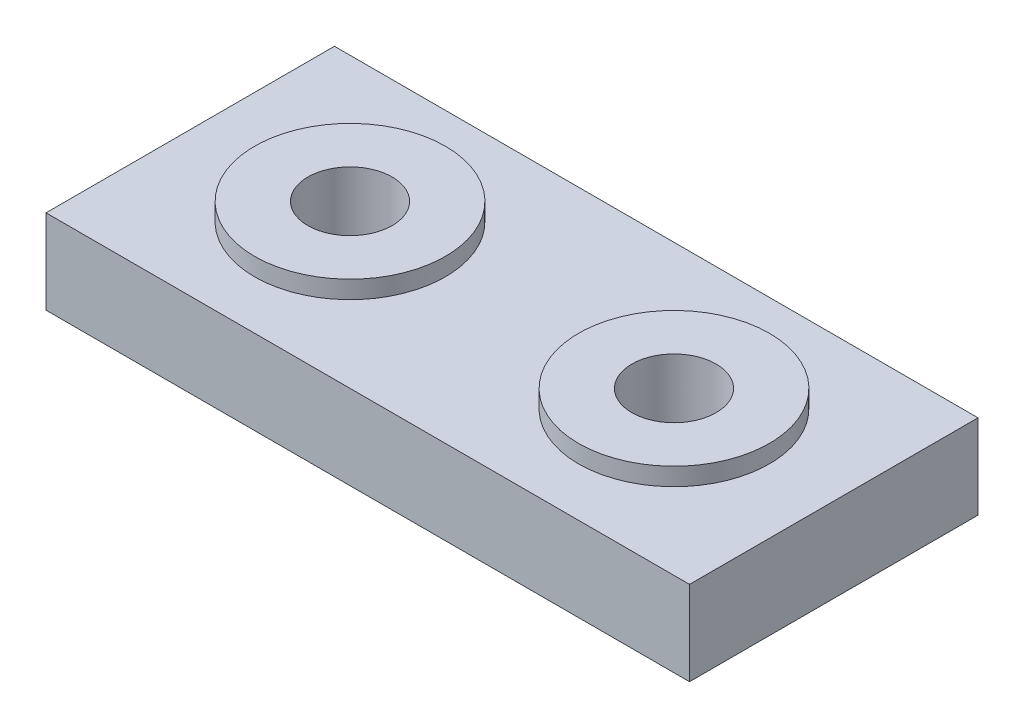
SolidWorks part; units mm, degrees
ref_plane "Front Plane" through (0, 0, 0) normal (0, 0, 1) x (1, 0, 0)
ref_plane "Top Plane" through (0, 0, 0) normal (0, 1, 0) x (1, 0, 0)
ref_plane "Right Plane" through (0, 0, 0) normal (1, 0, 0) x (0, 0, -1)
sketch "Sketch1" plane through (0, 0, 0) normal (0, 1, 0) x (1, 0, 0)
  line L1 (7.25, -3.25) -> (-7.25, -3.25)
  line L2 (7.25, -3.25) -> (7.25, 3.25)
  line L3 (7.25, 3.25) -> (-7.25, 3.25)
  line L4 (-7.25, -3.25) -> (-7.25, 3.25)
  line L5 (7.25, -3.25) -> (-7.25, 3.25) construction
  line L6 (7.25, 3.25) -> (-7.25, -3.25) construction
  point P0 (0, 0)
  dimension "D1" = 6.5
  dimension "D2" = 14.5
extrude "Boss-Extrude1" add sketch "Sketch1" along normal blind 1.9
shell "Shell1" thickness 1.2 removed face at (0, 0, 0)
sketch "Sketch2" plane through (0, 1.9, 0) normal (0, 1, 0) x (1, 0, 0)
  line L0 (-9.3255, 0) -> (9.5234, 0) construction
  line L1 (-7.25, 3.25) -> (-7.25, -3.25) construction
  line L2 (0, 0) -> (0, -3.8656) construction
  circle A0 centre (-3.65, 0) radius 2.15
  circle A1 centre (-3.65, 0) radius 0.95
  circle A2 centre (3.65, 0) radius 0.95
  circle A3 centre (3.65, 0) radius 2.15
  dimension "D1" = 4.3
  dimension "D3" = 1.2
  dimension "D2" = 3.6
extrude "Boss-Extrude2" add sketch "Sketch2" along normal blind 0.4
sketch "Sketch3" plane through (0, 1.9, 0) normal (0, 1, 0) x (1, 0, 0)
  circle A1 centre (-3.65, 0) radius 0.95
extrude "Cut-Extrude1" cut sketch "Sketch3" against normal blind 3.4
sketch "Sketch4" plane through (0, 1.9, 0) normal (0, 1, 0) x (1, 0, 0)
  circle A1 centre (3.65, 0) radius 0.95
extrude "Cut-Extrude2" cut sketch "Sketch4" against normal blind 3.4
